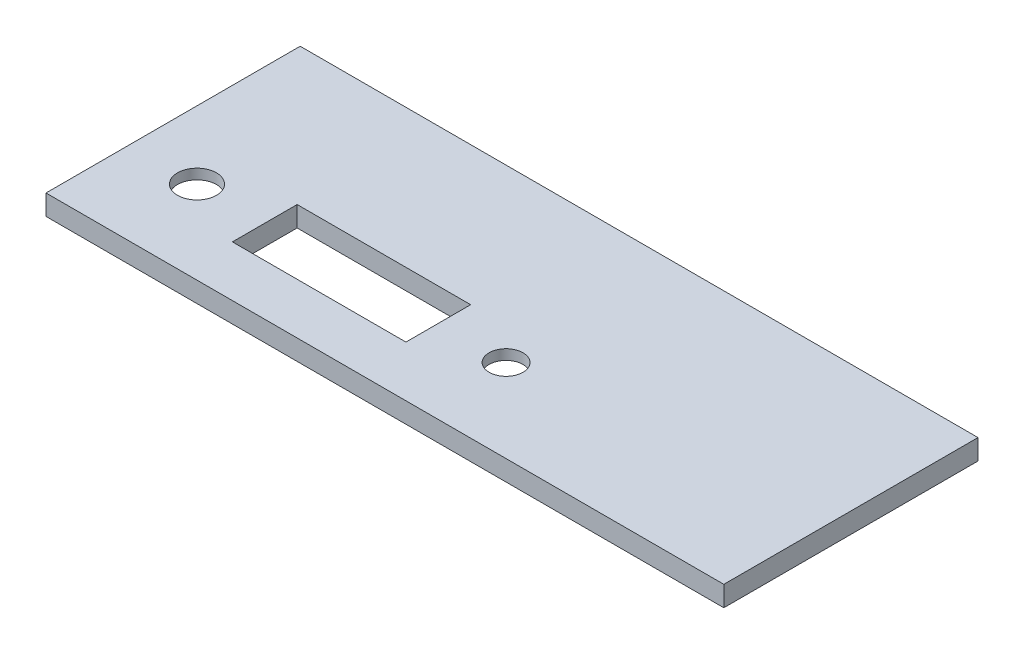
SolidWorks part; units mm, degrees
material "Pine"
ref_plane "Front Plane" through (0, 0, 0) normal (0, 0, 1) x (1, 0, 0)
ref_plane "Top Plane" through (0, 0, 0) normal (0, 1, 0) x (1, 0, 0)
ref_plane "Right Plane" through (0, 0, 0) normal (1, 0, 0) x (0, 0, -1)
sketch "Sketch1" plane through (0, 0, 0) normal (0, 1, 0) x (1, 0, 0)
  line L1 (0, 0) -> (200, 0)
  line L2 (0, 0) -> (0, 75)
  line L3 (0, 75) -> (200, 75)
  line L4 (200, 0) -> (200, 75)
  dimension "D1" = 75
  dimension "D2" = 200
extrude "Boss-Extrude1" add sketch "Sketch1" along normal blind 6
sketch "Sketch2" plane through (0, 6, 0) normal (0, 1, 0) x (1, 0, 0)
  line L0 (0, 0) -> (200, 0) construction
  line L1 (40, 15) -> (91.2, 15)
  line L2 (40, 15) -> (40, 34.1)
  line L3 (40, 34.1) -> (91.2, 34.1)
  line L4 (91.2, 15) -> (91.2, 34.1)
  line L5 (0, 75) -> (0, 0) construction
  line L6 (80.18, 24.55) -> (20, 24.55) construction
  circle A0 centre (20, 24.55) radius 5.75
  circle A1 centre (111.2, 24.55) radius 5
  point P14 (40, 24.55)
  dimension "D5" = 11.5
  dimension "D6" = 10
  dimension "D1" = 15
  dimension "D2" = 20
  dimension "D3" = 51.2
  dimension "D4" = 19.1
  dimension "D7" = 20
  dimension "D8" = 20
extrude "Cut-Extrude1" cut sketch "Sketch2" against normal through all
sketch "Sketch3" plane through (0, 0, 0) normal (0, -1, 0) x (1, 0, 0)
  circle A0 centre (20, -24.55) radius 10
  dimension "D1" = 20
extrude "Cut-Extrude2" cut sketch "Sketch3" against normal blind 3
sketch "Sketch4" plane through (0, 0, 0) normal (0, -1, 0) x (1, 0, 0)
  circle A0 centre (111.2, -24.55) radius 10
  dimension "D1" = 20
extrude "Cut-Extrude3" cut sketch "Sketch4" against normal blind 3
equation "\"BoardThickness\"= 6"
equation "\"D1@Boss-Extrude1\"=\"BoardThickness\""
equation "\"D1@Cut-Extrude2\"=\"BoardThickness\"*0.5"
equation "\"D1@Cut-Extrude3\"=\"BoardThickness\"/2"
